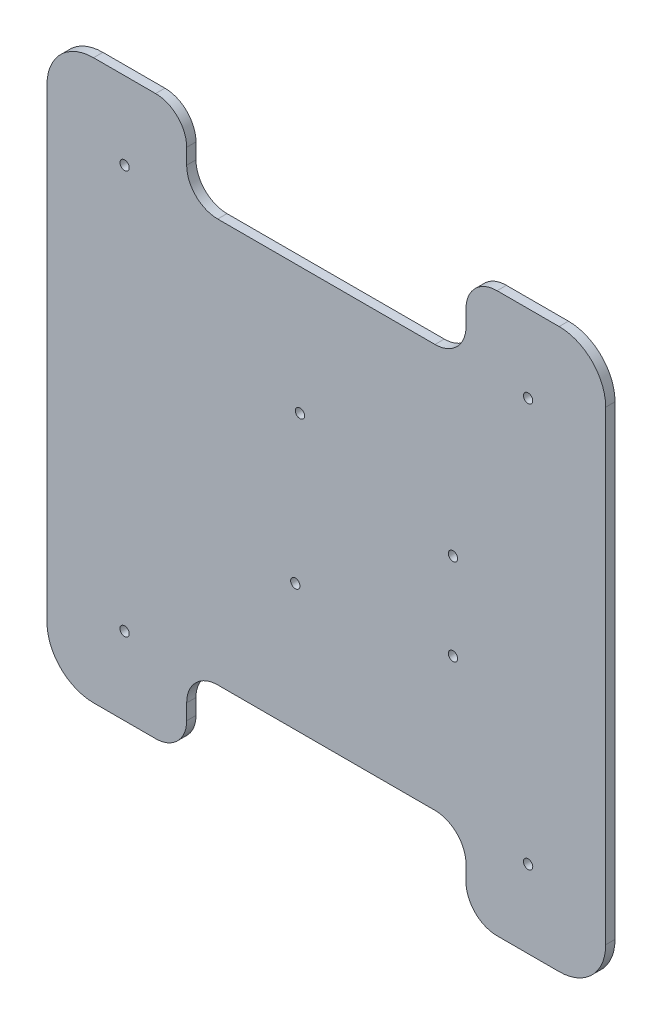
SolidWorks part; units mm, degrees
ref_plane "Front" through (0, 0, 0) normal (0, 0, 1) x (1, 0, 0)
ref_plane "Top" through (0, 0, 0) normal (0, 1, 0) x (1, 0, 0)
ref_plane "Right" through (0, 0, 0) normal (1, 0, 0) x (0, 0, -1)
sketch "Эскиз1" plane through (0, 0, 0) normal (0, 0, 1) x (1, 0, 0)
  line L1 (75, -90) -> (-75, -90)
  line L2 (90, -75) -> (90, 75)
  line L3 (75, 90) -> (-75, 90)
  line L4 (-90, -75) -> (-90, 75)
  line L5 (90, -90) -> (-90, 90) construction
  line L6 (90, 90) -> (-90, -90) construction
  arc A0 (-75, -90) -> (-90, -75) centre (-75, -75) cw
  arc A1 (75, -90) -> (90, -75) centre (75, -75) ccw
  arc A2 (90, 75) -> (75, 90) centre (75, 75) ccw
  arc A3 (-90, 75) -> (-75, 90) centre (-75, 75) cw
  point P0 (0, 0)
  dimension "D3" = 15
  dimension "D1" = 180
  dimension "D2" = 180
extrude "Бобышка-Вытянуть1" add sketch "Эскиз1" along normal blind 3
hole_wizard "Диаметр отверстия Ø3.0 (3)1" positions "Эскиз5" profile "Эскиз4" hole size "Ø3.0" standard "Ansi Metric" end condition up to next
sketch "Эскиз5" plane through (0, 0, 3) normal (0, 0, 1) x (1, 0, 0)
  line L4 (-90, 0) -> (-10, 0) construction
  line L5 (-90, 75) -> (-90, -75) construction
  line L6 (-10, 0) -> (40.8, 0) construction
  line L7 (40.8, 0) -> (90, 0) construction
  line L8 (90, -75) -> (90, 75) construction
  line L10 (-10, -26.65) -> (-10, 26.65) construction
  line L12 (40.8, -19.05) -> (40.8, 8.85) construction
  line L13 (-10, 24.05) -> (-8.5, 24.05) construction
  point P33 (-10, -24.15)
  point P45 (40.8, 8.85)
  point P48 (40.8, -19.05)
  point P59 (-8.5, 24.05)
  dimension "D1" = 53.3
  dimension "D2" = 50.8
  dimension "D3" = 27.9
  dimension "D4" = 2.5
  dimension "D5" = 5.1
  dimension "D6" = 1.5
  dimension "D7" = 80
  dimension "D8" = 15.2
sketch "Эскиз4" plane through (-10, -24.15, 3) normal (1, 0, 0) x (0, -1, 0)
  line L0 (0, 0) -> (0, 3)
  line L1 (0, 3) -> (1.5, 3)
  line L2 (1.5, 3) -> (1.5, 0)
  line L5 (1.5, 0) -> (0, 0)
  line L11 (0, -6.35) -> (0, 107.95) construction
  dimension "Диаметр сквозного отверстия" = 3
  dimension "Глубина сквозного отверстия" = 3
sketch "Эскиз7" plane through (0, 0, 3) normal (0, 0, 1) x (1, 0, 0)
  line L0 (0, -90) -> (0, 90) construction
  line L1 (-75, -90) -> (75, -90) construction
  line L2 (75, 90) -> (-75, 90) construction
  line L4 (45, 65) -> (-45, 65)
  line L5 (45, 65) -> (45, 90)
  line L6 (45, 90) -> (-45, 90)
  line L7 (-45, 65) -> (-45, 90)
  line L8 (45, 65) -> (-45, 90) construction
  line L9 (45, 90) -> (-45, 65) construction
  line L10 (45, -65) -> (-45, -65)
  line L11 (45, -65) -> (45, -90)
  line L12 (45, -90) -> (-45, -90)
  line L13 (-45, -65) -> (-45, -90)
  line L14 (45, -65) -> (-45, -90) construction
  line L15 (45, -90) -> (-45, -65) construction
  point P6 (0, 77.5)
  point P11 (0, -77.5)
  dimension "D1" = 90
  dimension "D2" = 25
extrude "Вырез-Вытянуть1" cut sketch "Эскиз7" against normal through all
fillet "Скругление7" radius 10 8 edges at (45, -90, 1.5) (45, -65, 1.5) (-45, -65, 1.5) (-45, -90, 1.5) (45, 65, 1.5) (45, 90, 1.5) (-45, 90, 1.5) (-45, 65, 1.5)
hole_wizard "Диаметр отверстия Ø3.0 (3)2" positions "Эскиз9" profile "Эскиз8" hole size "Ø3.0" standard "Ansi Metric" end condition up to next
sketch "Эскиз9" plane through (0, 0, 3) normal (0, 0, 1) x (1, 0, 0)
  line L8 (65, -90) -> (65, -65) construction
  line L9 (55, -90) -> (75, -90) construction
  line L10 (65, -65) -> (65, 65) construction
  line L11 (65, 65) -> (65, 90) construction
  line L12 (75, 90) -> (55, 90) construction
  line L14 (-65, 90) -> (-65, 65) construction
  line L15 (-55, 90) -> (-75, 90) construction
  line L16 (-65, 65) -> (-65, -65) construction
  line L17 (-65, -65) -> (-65, -90) construction
  line L18 (-75, -90) -> (-55, -90) construction
  line L20 (-65, -65) -> (-90, -65) construction
  line L21 (-90, 75) -> (-90, -75) construction
  point P50 (-65, -65)
  point P53 (65, -65)
  point P56 (65, 65)
  point P61 (-65, 65)
sketch "Эскиз8" plane through (-65, -65, 3) normal (1, 0, 0) x (0, -1, 0)
  line L0 (0, 0) -> (0, 3)
  line L1 (0, 3) -> (1.5, 3)
  line L2 (1.5, 3) -> (1.5, 0)
  line L5 (1.5, 0) -> (0, 0)
  line L11 (0, -6.35) -> (0, 107.95) construction
  dimension "Диаметр сквозного отверстия" = 3
  dimension "Глубина сквозного отверстия" = 3
